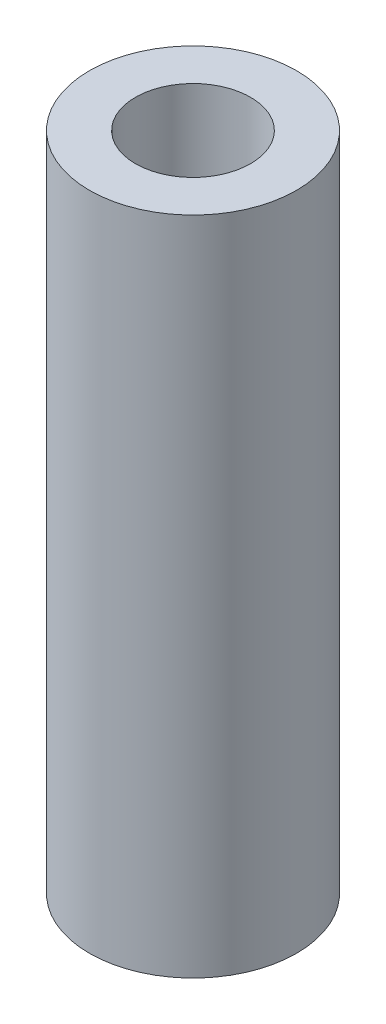
SolidWorks part; units mm, degrees
ref_plane "Front Plane" through (0, 0, 0) normal (0, 0, 1) x (1, 0, 0)
ref_plane "Top Plane" through (0, 0, 0) normal (0, 1, 0) x (1, 0, 0)
ref_plane "Right Plane" through (0, 0, 0) normal (1, 0, 0) x (0, 0, -1)
sketch "Sketch1" plane through (0, 0, 0) normal (0, 1, 0) x (1, 0, 0)
  circle A2 centre (0, 0) radius 3.175
  circle A4 centre (0, 0) radius 5.715
  dimension "D3" = 6.35
  dimension "D1" = 2.54
extrude "Boss-Extrude1" add sketch "Sketch1" along normal mid plane 36.449
